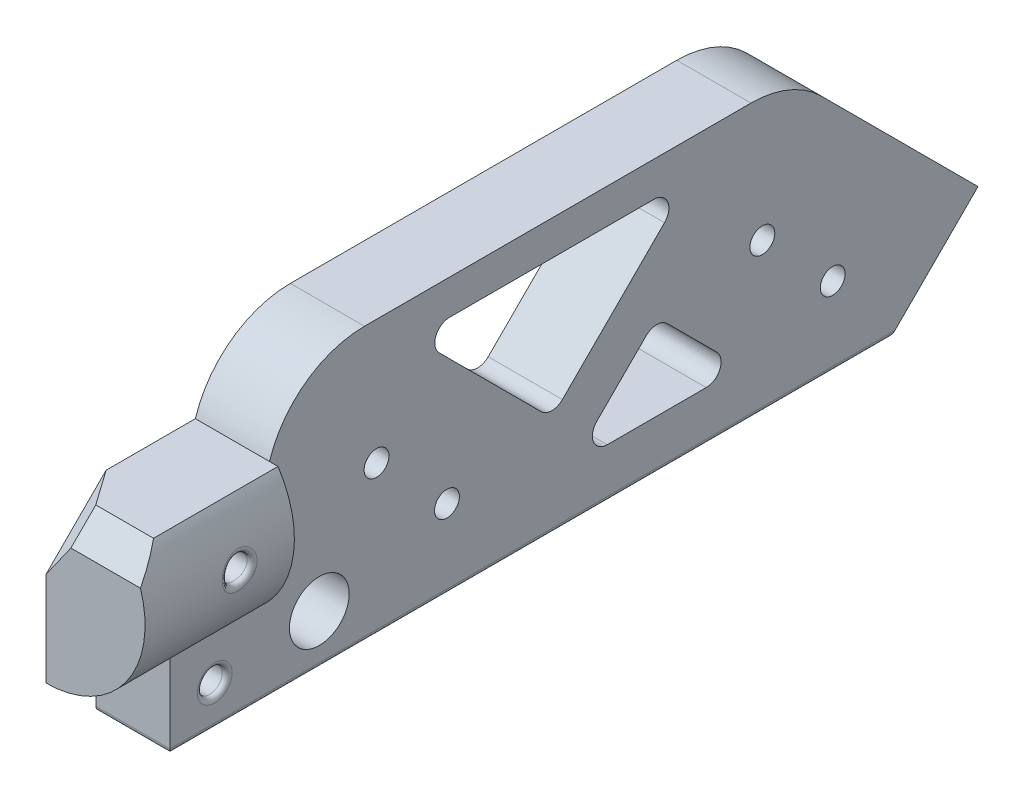
SolidWorks part; units mm, degrees
ref_plane "前视基准面" through (0, 0, 0) normal (0, 0, 1) x (1, 0, 0)
ref_plane "上视基准面" through (0, 0, 0) normal (0, 1, 0) x (1, 0, 0)
ref_plane "右视基准面" through (0, 0, 0) normal (1, 0, 0) x (0, 0, -1)
sketch "草图1" plane through (0, 0, 0) normal (0, 0, 1) x (1, 0, 0)
  line L0 (16.7033, 11) -> (-16.7033, 11)
  arc A0 (-16.7033, 11) -> (16.7033, 11) centre (0, 0) ccw
  dimension "D1" = 40
  dimension "D2" = 11
extrude "凸台-拉伸1" add sketch "草图1" along normal blind 21
sketch "草图2" plane through (0, 0, 21) normal (0, 0, 1) x (1, 0, 0)
  line L1 (10, -10) -> (-10, -10)
  line L2 (10, -10) -> (10, 10)
  line L3 (10, 10) -> (-10, 10)
  line L4 (-10, -10) -> (-10, 10)
  line L5 (10, -10) -> (-10, 10) construction
  line L6 (10, 10) -> (-10, -10) construction
  point P0 (0, 0)
  dimension "D1" = 20
  dimension "D2" = 20
extrude "切除-拉伸1" cut sketch "草图2" against normal blind 10
sketch "草图3" plane through (0, 0, 0) normal (0, 0, -1) x (-1, 0, 0)
  line L1 (16.7033, 11) -> (-16.7033, 11)
  line L2 (16.7033, 11) -> (-16.7033, 11)
  circle A0 centre (0, 0) radius 25
  arc A1 (-16.7033, 11) -> (16.7033, 11) centre (0, 0) ccw
  arc A2 (-16.7033, 11) -> (16.7033, 11) centre (0, 0) ccw
  dimension "D2" = 50
  dimension "D1" = 0
extrude "凸台-拉伸2" add sketch "草图3" against normal blind 2
sketch "草图4" plane through (0, 0, 11) normal (0, 0, 1) x (1, 0, 0)
  line L4 (-10, 10) -> (-10, -10)
  line L5 (-10, -10) -> (10, -10)
  line L6 (10, -10) -> (10, 10)
  line L7 (10, 10) -> (-10, 10)
  line L8 (-10, 10) -> (-10, -10)
  line L9 (-10, -10) -> (10, -10)
  line L10 (10, -10) -> (10, 10)
  line L11 (10, 10) -> (-10, 10)
  dimension "D1" = 0
extrude "切除-拉伸2" cut sketch "草图4" against normal blind 20
sketch "草图5" plane through (0, 11, 0) normal (0, 1, 0) x (1, 0, 0)
  line L1 (-33.8348, 26.2279) -> (33.8348, 26.2279)
  line L2 (-33.8348, 26.2279) -> (-33.8348, -26.2279)
  line L3 (-33.8348, -26.2279) -> (33.8348, -26.2279)
  line L4 (33.8348, 26.2279) -> (33.8348, -26.2279)
  line L5 (-33.8348, 26.2279) -> (33.8348, -26.2279) construction
  line L6 (-33.8348, -26.2279) -> (33.8348, 26.2279) construction
  point P0 (0, 0)
extrude "切除-拉伸3" cut sketch "草图5" along normal blind 22
sketch "草图6" plane through (0, 0, 0) normal (0, 1, 0) x (1, 0, 0)
  line L0 (-20, -21) -> (20, -21) construction
  line L1 (20, -21) -> (20, -2) construction
  circle A0 centre (0, -13) radius 2.55
  dimension "D1" = 5.1
  dimension "D2" = 8
  dimension "D3" = 20
extrude "切除-拉伸4" [suppressed] cut sketch "草图6" against normal blind 22
pattern_circular "阵列(圆周)1" [suppressed] count 4 over 360 of bodies 111
sketch "草图7" plane through (0, 0, 21) normal (0, 0, 1) x (1, 0, 0)
  line L0 (-3.3541, 11) -> (-16.7033, 11)
  line L1 (16.7033, 11) -> (-16.7033, 11)
  line L5 (16.7033, 11) -> (-16.7033, 11)
  arc A0 (-3.3541, 11) -> (3.3541, 11) centre (0, 0) ccw
  arc A1 (-16.7033, 11) -> (16.7033, 11) centre (0, 0) ccw
  arc A5 (-16.7033, 11) -> (16.7033, 11) centre (0, 0) ccw
  dimension "22.5" = 23
  dimension "D1" = 0
extrude "凸台-拉伸3" [suppressed] add sketch "草图7" along normal blind 1
sketch "草图8" [suppressed] plane through (0, 0, 21) normal (0, 0, 1) x (1, 0, 0)
  circle A0 centre (0, 20) radius 12
  dimension "D2" = 24
  dimension "D1" = 20
extrude "切除-拉伸5" [suppressed] cut sketch "草图8" against normal up to surface (1 mm away)
fillet "圆角1" [suppressed] radius 3
sketch "草图9" [suppressed] plane through (0, 0, 21) normal (0, 0, 1) x (1, 0, 0)
  line L2 (16.7033, 11) -> (7.9373, 11)
  line L3 (-7.9373, 11) -> (-16.7033, 11)
  line L4 (16.7033, 11) -> (7.9373, 11)
  line L5 (-7.9373, 11) -> (-16.7033, 11)
  arc A4 (7.9373, 11) -> (8.4758, 7.7725) centre (10.6868, 9.8001) ccw
  arc A5 (-8.4758, 7.7725) -> (8.4758, 7.7725) centre (0, 0) ccw
  arc A6 (-8.4758, 7.7725) -> (-7.9373, 11) centre (-10.6868, 9.8001) ccw
  arc A7 (-16.7033, 11) -> (16.7033, 11) centre (0, 0) ccw
  arc A8 (7.9373, 11) -> (8.4758, 7.7725) centre (10.6868, 9.8001) ccw
  arc A9 (-8.4758, 7.7725) -> (8.4758, 7.7725) centre (0, 0) ccw
  arc A10 (-8.4758, 7.7725) -> (-7.9373, 11) centre (-10.6868, 9.8001) ccw
  arc A11 (-16.7033, 11) -> (16.7033, 11) centre (0, 0) ccw
  dimension "D1" = 0
extrude "凸台-拉伸4" [suppressed] add sketch "草图9" along normal blind 1
sketch "草图10" plane through (0, 0, 21) normal (0, 0, 1) x (1, 0, 0)
  line L1 (16.7033, 11) -> (-16.7033, 11)
  line L2 (16.7033, 11) -> (-16.7033, 11)
  arc A1 (-16.7033, 11) -> (16.7033, 11) centre (0, 0) ccw
  arc A2 (-16.7033, 11) -> (16.7033, 11) centre (0, 0) ccw
  dimension "D1" = 0
extrude "凸台-拉伸5" add sketch "草图10" along normal blind 1
sketch "草图11" plane through (0, 0, 21) normal (0, 0, -1) x (-1, 0, 0)
  line L0 (-10, 10) -> (10, 10) construction
  line L1 (-3, 24) -> (3, 24)
  line L2 (-3, 24) -> (-3, -4)
  line L3 (-3, -4) -> (3, -4)
  line L4 (3, 24) -> (3, -4)
  line L5 (-3, 24) -> (3, -4) construction
  line L6 (-3, -4) -> (3, 24) construction
  point P0 (0, 10)
  dimension "D1" = 6
  dimension "D2" = 28
extrude "切除-拉伸6" [suppressed] cut sketch "草图11" against normal blind 1
sketch "草图12" plane through (0, 0, 21) normal (0, 0, -1) x (-1, 0, 0)
  line L11 (10, 10) -> (-10, 10)
  line L12 (-10, 10) -> (-10, -10)
  line L13 (-10, -10) -> (10, -10)
  line L14 (10, -10) -> (10, 10)
  line L19 (10, 10) -> (-10, 10)
  line L20 (-10, 10) -> (-10, -10)
  line L21 (-10, -10) -> (10, -10)
  line L22 (10, -10) -> (10, 10)
  dimension "D1" = 0
extrude "凸台-拉伸6" [suppressed] add sketch "草图12" along normal blind 1
sketch "草图13" [suppressed] plane through (0, 0, 20) normal (0, 0, -1) x (-1, 0, 0)
  circle A0 centre (0, 0) radius 2.5
  dimension "D1" = 5
extrude "切除-拉伸7" [suppressed] cut sketch "草图13" against normal blind 44
sketch "草图14" [suppressed] plane through (0, 0, 22) normal (0, 0, 1) x (1, 0, 0)
  line L1 (-2.5, 5) -> (2.5, 5)
  line L2 (-2.5, 5) -> (-2.5, 0)
  line L3 (-2.5, 0) -> (2.5, 0)
  line L4 (2.5, 5) -> (2.5, 0)
  line L5 (-2.5, 5) -> (2.5, 0) construction
  line L6 (-2.5, 0) -> (2.5, 5) construction
  circle A0 centre (0, 0) radius 2.5 construction
  point P0 (0, 2.5)
  dimension "D1" = 5
extrude "切除-拉伸8" [suppressed] cut sketch "草图14" against normal blind 1
sketch "草图15" [suppressed] plane through (0, 0, 22) normal (0, 0, 1) x (1, 0, 0)
  line L0 (2.5, 5) -> (-2.5, 5) construction
  circle A0 centre (0, 5) radius 2.5
extrude "切除-拉伸9" [suppressed] cut sketch "草图15" against normal blind 1
sketch "草图16" [suppressed] plane through (0, 0, 22) normal (0, 0, 1) x (1, 0, 0)
  line L0 (16.7033, 11) -> (-16.7033, 11) construction
  line L1 (-2.5, 5) -> (2.5, 5)
  line L2 (-2.5, 5) -> (-2.5, 11)
  line L3 (-2.5, 11) -> (2.5, 11)
  line L4 (2.5, 5) -> (2.5, 11)
  dimension "D1" = 5
extrude "切除-拉伸10" [suppressed] cut sketch "草图16" against normal blind 1
sketch "草图17" [suppressed] plane through (0, 0, 21) normal (0, 0, 1) x (1, 0, 0)
  circle A0 centre (0, 7) radius 2.5
  dimension "D1" = 5
  dimension "D2" = 7
extrude "切除-拉伸11" [suppressed] cut sketch "草图17" against normal blind 6
fillet "圆角2" [suppressed] radius 0.5
fillet "圆角3" [suppressed] radius 1
sketch "草图18" plane through (0, 0, 2) normal (0, 0, 1) x (1, 0, 0)
  line L2 (-16.7033, 11) -> (-22.4499, 11)
  line L3 (22.4499, 11) -> (16.7033, 11)
  line L4 (-16.7033, 11) -> (-22.4499, 11)
  line L5 (22.4499, 11) -> (16.7033, 11)
  arc A2 (-22.4499, 11) -> (22.4499, 11) centre (0, 0) ccw
  arc A3 (-16.7033, 11) -> (16.7033, 11) centre (0, 0) ccw
  arc A4 (-22.4499, 11) -> (22.4499, 11) centre (0, 0) ccw
  arc A5 (-16.7033, 11) -> (16.7033, 11) centre (0, 0) ccw
  dimension "D1" = 0
extrude "切除-拉伸12" cut sketch "草图18" against normal blind 6
sketch "草图19" plane through (0, 0, 0) normal (0, 0, -1) x (-1, 0, 0)
  line L1 (16.7033, 11) -> (-16.7033, 11)
  line L2 (16.7033, 11) -> (-16.7033, 11)
  arc A1 (-16.7033, 11) -> (16.7033, 11) centre (0, 0) ccw
  arc A4 (-16.7033, 11) -> (16.7033, 11) centre (0, 0) ccw
  dimension "D1" = 0
extrude "切除-拉伸13" cut sketch "草图19" against normal blind 2
sketch "草图20" [suppressed] plane through (0, 11, 0) normal (0, 1, 0) x (1, 0, 0)
  line L1 (-2.55, -13) -> (2.55, -13)
  line L2 (-2.55, -13) -> (-2.55, 0.9444)
  line L3 (-2.55, 0.9444) -> (2.55, 0.9444)
  line L4 (2.55, -13) -> (2.55, 0.9444)
  circle A0 centre (0, -13) radius 2.55 construction
  dimension "D1" = 5.1
extrude "切除-拉伸14" [suppressed] cut sketch "草图20" against normal blind 2
sketch "草图21" plane through (0, 0, 21) normal (0, 0, -1) x (-1, 0, 0)
  line L4 (10, -10) -> (10, 10)
  line L5 (10, 10) -> (-10, 10)
  line L6 (-10, 10) -> (-10, -10)
  line L7 (-10, -10) -> (10, -10)
  line L8 (10, -10) -> (10, 10)
  line L9 (10, 10) -> (-10, 10)
  line L10 (-10, 10) -> (-10, -10)
  line L11 (-10, -10) -> (10, -10)
  dimension "D1" = 0
extrude "凸台-拉伸7" add sketch "草图21" along normal up to surface (19 mm away) up to face at (0, -4.5, 2)
sketch "草图22" plane through (0, 0, 2) normal (0, 0, -1) x (-1, 0, 0)
  line L1 (-15, -10) -> (15, -10)
  line L2 (-15, -10) -> (-15, -30)
  line L3 (-15, -30) -> (15, -30)
  line L4 (15, -10) -> (15, -30)
  line L5 (-15, -10) -> (15, -30) construction
  line L6 (-15, -30) -> (15, -10) construction
  arc A0 (-16.7033, 11) -> (16.7033, 11) centre (0, 0) ccw construction
  point P0 (0, -20)
  dimension "D1" = 30
  dimension "D2" = 20
extrude "凸台-拉伸8" add sketch "草图22" against normal blind 10
sketch "草图23" plane through (0, 0, 2) normal (0, 0, -1) x (-1, 0, 0)
  line L4 (-15, -13.2288) -> (-15, -30)
  line L5 (-15, -30) -> (15, -30)
  line L6 (15, -30) -> (15, -13.2288)
  line L7 (16.7033, 11) -> (-16.7033, 11)
  line L8 (-15, -13.2288) -> (-15, -30)
  line L9 (-15, -30) -> (15, -30)
  line L10 (15, -30) -> (15, -13.2288)
  line L11 (16.7033, 11) -> (-16.7033, 11)
  arc A2 (-16.7033, 11) -> (-15, -13.2288) centre (0, 0) ccw
  arc A3 (15, -13.2288) -> (16.7033, 11) centre (0, 0) ccw
  arc A4 (-16.7033, 11) -> (-15, -13.2288) centre (0, 0) ccw
  arc A5 (15, -13.2288) -> (16.7033, 11) centre (0, 0) ccw
  dimension "D1" = 0
extrude "凸台-拉伸9" add sketch "草图23" along normal blind 10
sketch "草图24" plane through (0, 0, -8) normal (0, 0, -1) x (-1, 0, 0)
  line L1 (-15, -30) -> (15, -30)
  line L2 (-15, -30) -> (-15, 20)
  line L3 (-15, 20) -> (15, 20)
  line L4 (15, -30) -> (15, 20)
  dimension "D1" = 30
  dimension "D2" = 50
extrude "凸台-拉伸10" add sketch "草图24" along normal blind 160
sketch "草图26" plane through (-15, 0, 0) normal (-1, 0, 0) x (0, 0, 1)
  line L0 (-8, -13.2288) -> (-8, 11) construction
  circle A0 centre (-107, 0) radius 2.5
  circle A1 centre (-29.5, 0) radius 2.5
  dimension "D1" = 5
  dimension "D2" = 99
  dimension "D3" = 77.5
extrude "切除-拉伸15" cut sketch "草图26" against normal blind 50
sketch "草图27" plane through (0, 0, 0) normal (1, 0, 0) x (0, 0, -1)
  line L0 (96.3934, 10.6066) -> (145.8909, -38.8909)
  line L1 (-12, -30) -> (168, -30) construction
  line L2 (18.8934, 10.6066) -> (68.3909, -38.8909)
  circle A0 centre (107, 0) radius 2.5 construction
  dimension "D1" = 15
  dimension "D2" = 45
  dimension "D3" = 70
extrude "切除-拉伸-薄壁1" cut sketch "草图27" against normal blind 10 and the other way blind 10 thin thin type mid plane wall 20
sketch "草图28" plane through (0, 20, 0) normal (0, 1, 0) x (1, 0, 0)
  line L4 (-15, 8) -> (15, 8)
  line L5 (15, 8) -> (15, 168)
  line L6 (15, 168) -> (-15, 168)
  line L7 (-15, 168) -> (-15, 8)
  line L8 (-15, 8) -> (15, 8)
  line L9 (15, 8) -> (15, 168)
  line L10 (15, 168) -> (-15, 168)
  line L11 (-15, 168) -> (-15, 8)
  dimension "D1" = 0
extrude "凸台-拉伸11" add sketch "草图28" along normal blind 5
sketch "草图29" plane through (-15, 0, 0) normal (-1, 0, 0) x (0, 0, 1)
  circle A0 centre (3, 0) radius 2.5
  circle A1 centre (3, -22) radius 2.5
  dimension "D1" = 5
  dimension "D2" = 5
extrude "切除-拉伸16" cut sketch "草图29" against normal blind 60 and the other way blind 25
sketch "草图30" plane through (-15, 0, 0) normal (-1, 0, 0) x (0, 0, 1)
  line L0 (-113, 25) -> (-168, -30)
  line L1 (-168, 25) -> (-8, 25) construction
  line L2 (-168, -30) -> (-168, 25) construction
  line L3 (-168, -30) -> (-168, 25)
  line L4 (-168, 25) -> (-113, 25)
  dimension "D1" = 45
  dimension "D2" = 55
extrude "切除-拉伸17" cut sketch "草图30" against normal blind 60
sketch "草图31" plane through (0, 0, 0) normal (1, 0, 0) x (0, 0, -1)
  line L0 (92.4731, 18) -> (64.7145, -9.7586)
  line L1 (64.7145, -9.7586) -> (36.9558, 18)
  line L2 (36.9558, 18) -> (92.4731, 18)
  line L3 (8, 25) -> (113, 25) construction
  line L4 (89.3223, 3.5355) -> (103.4645, 17.6777) construction
  line L6 (25.9645, 17.6777) -> (73.6421, -30) construction
  dimension "D1" = 7
  dimension "D2" = 8
  dimension "D3" = 90
  dimension "D4" = 8
extrude "切除-拉伸18" cut sketch "草图31" against normal blind 60 and the other way blind 60
sketch "草图32" plane through (0, 0, 0) normal (1, 0, 0) x (0, 0, -1)
  line L0 (85.7868, -2.8284) -> (102.9584, -20)
  line L1 (102.9584, -20) -> (68.6152, -20)
  line L2 (68.6152, -20) -> (85.7868, -2.8284)
  line L3 (89.3223, 3.5355) -> (122.8579, -30) construction
  line L4 (-12, -30) -> (168, -30) construction
  line L5 (92.4731, 18) -> (64.7145, -9.7586) construction
  dimension "D1" = 7
  dimension "D2" = 10
  dimension "D3" = 10
extrude "切除-拉伸19" cut sketch "草图32" against normal blind 60 and the other way blind 60
fillet "圆角4" radius 3 6 edges at (0, -2.8284, -85.7868) (0, -20, -102.9584) (0, -20, -68.6152) (0, 18, -36.9558) (0, 18, -92.4731) (0, -9.7586, -64.7145)
sketch "草图33" plane through (0, 0, 0) normal (1, 0, 0) x (0, 0, -1)
  line L0 (-12, -30) -> (168, -30) construction
  line L1 (-12, -13.2288) -> (-12, -30) construction
  circle A0 centre (18, -20) radius 6
  dimension "D1" = 12
  dimension "D2" = 10
  dimension "D3" = 30
extrude "切除-拉伸20" cut sketch "草图33" against normal blind 60 and the other way blind 60
sketch "草图34" plane through (-15, 0, 0) normal (-1, 0, 0) x (0, 0, 1)
  line L0 (-150.3223, -12.3223) -> (-132.6447, -30)
  line L1 (-168, -30) -> (-113, 25) construction
  line L2 (12, -30) -> (-168, -30) construction
  line L3 (-132.6447, -30) -> (-168, -30)
  line L4 (-168, -30) -> (-150.3223, -12.3223)
  dimension "D1" = 45
  dimension "D2" = 25
extrude "切除-拉伸21" cut sketch "草图34" against normal blind 60
fillet "圆角5" radius 20 1 edges at (0, 25, -113)
sketch "草图35" plane through (-15, 0, 0) normal (-1, 0, 0) x (0, 0, 1)
  circle A0 centre (-29.5, 0) radius 2.5 construction
  circle A1 centre (-107, 0) radius 2.5 construction
  circle A2 centre (-29.5, 0) radius 2.5
  circle A3 centre (-107, 0) radius 2.5
  circle A4 centre (-121.1421, -14.1421) radius 2.5
  circle A5 centre (-43.6421, -14.1421) radius 2.5
  dimension "D1" = 2
extrude "切除-拉伸22" cut sketch "草图35" against normal blind 60
fillet "圆角6" radius 20 1 edges at (0, 25, -8)
sketch "草图36" plane through (0, 0, 0) normal (1, 0, 0) x (0, 0, -1)
  line L1 (-64.6972, -126.234) -> (192.7695, -126.234)
  line L2 (-64.6972, -126.234) -> (-64.6972, 60.9918)
  line L3 (-64.6972, 60.9918) -> (192.7695, 60.9918)
  line L4 (192.7695, -126.234) -> (192.7695, 60.9918)
  line L5 (-64.6972, -126.234) -> (192.7695, 60.9918) construction
  line L6 (-64.6972, 60.9918) -> (192.7695, -126.234) construction
  point P0 (64.0362, -32.6211)
extrude "切除-拉伸23" cut sketch "草图36" against normal blind 82
sketch "草图37" plane through (0, 0, 0) normal (-1, 0, 0) x (0, 0, 1)
  line L15 (-11.8223, 3.5355) -> (-45.3579, -30)
  line L16 (-45.3579, -30) -> (12, -30)
  line L17 (12, -30) -> (12, -20)
  line L18 (12, -20) -> (22, -20)
  line L19 (22, -20) -> (22, 11)
  line L20 (22, 11) -> (-8, 11)
  line L21 (-27.0788, 25) -> (-104.7157, 25)
  line L22 (-118.8579, 19.1421) -> (-150.3223, -12.3223)
  line L23 (-150.3223, -12.3223) -> (-141.8934, -20.7513)
  line L24 (-141.8934, -20.7513) -> (-103.4645, 17.6777)
  line L25 (-103.4645, 17.6777) -> (-89.3223, 3.5355)
  line L26 (-89.3223, 3.5355) -> (-122.8579, -30)
  line L27 (-122.8579, -30) -> (-73.6421, -30)
  line L28 (-73.6421, -30) -> (-25.9645, 17.6777)
  line L29 (-25.9645, 17.6777) -> (-11.8223, 3.5355)
  line L30 (-11.8223, 3.5355) -> (-45.3579, -30)
  line L31 (-45.3579, -30) -> (12, -30)
  line L32 (12, -30) -> (12, -20)
  line L33 (12, -20) -> (22, -20)
  line L34 (22, -20) -> (22, 11)
  line L35 (22, 11) -> (-8, 11)
  line L36 (-27.0788, 25) -> (-104.7157, 25)
  line L37 (-118.8579, 19.1421) -> (-150.3223, -12.3223)
  line L38 (-150.3223, -12.3223) -> (-141.8934, -20.7513)
  line L39 (-141.8934, -20.7513) -> (-103.4645, 17.6777)
  line L40 (-103.4645, 17.6777) -> (-89.3223, 3.5355)
  line L41 (-89.3223, 3.5355) -> (-122.8579, -30)
  line L42 (-122.8579, -30) -> (-73.6421, -30)
  line L43 (-73.6421, -30) -> (-25.9645, 17.6777)
  line L44 (-25.9645, 17.6777) -> (-11.8223, 3.5355)
  arc A2 (-8, 11) -> (-27.0788, 25) centre (-27.0788, 5) ccw
  arc A3 (-104.7157, 25) -> (-118.8579, 19.1421) centre (-104.7157, 5) ccw
  arc A4 (-8, 11) -> (-27.0788, 25) centre (-27.0788, 5) ccw
  arc A5 (-104.7157, 25) -> (-118.8579, 19.1421) centre (-104.7157, 5) ccw
  dimension "D1" = 0
extrude "切除-拉伸24" cut sketch "草图37" against normal blind 0.1
fillet "圆角7" radius 1 2 edges at (15, -19.5, 3) (19.9924, -0.5531, 5.438)
fillet "圆角8" radius 1 2 edges at (15, -30, -60.3223) (7.55, -30, 12)
chamfer "倒角1" distance 5 angle 45 1 edges at (8.4016, 11, 22)
chamfer "倒角2" distance 5 angle 45 1 edges at (0.1, 8.5, 19.5)
